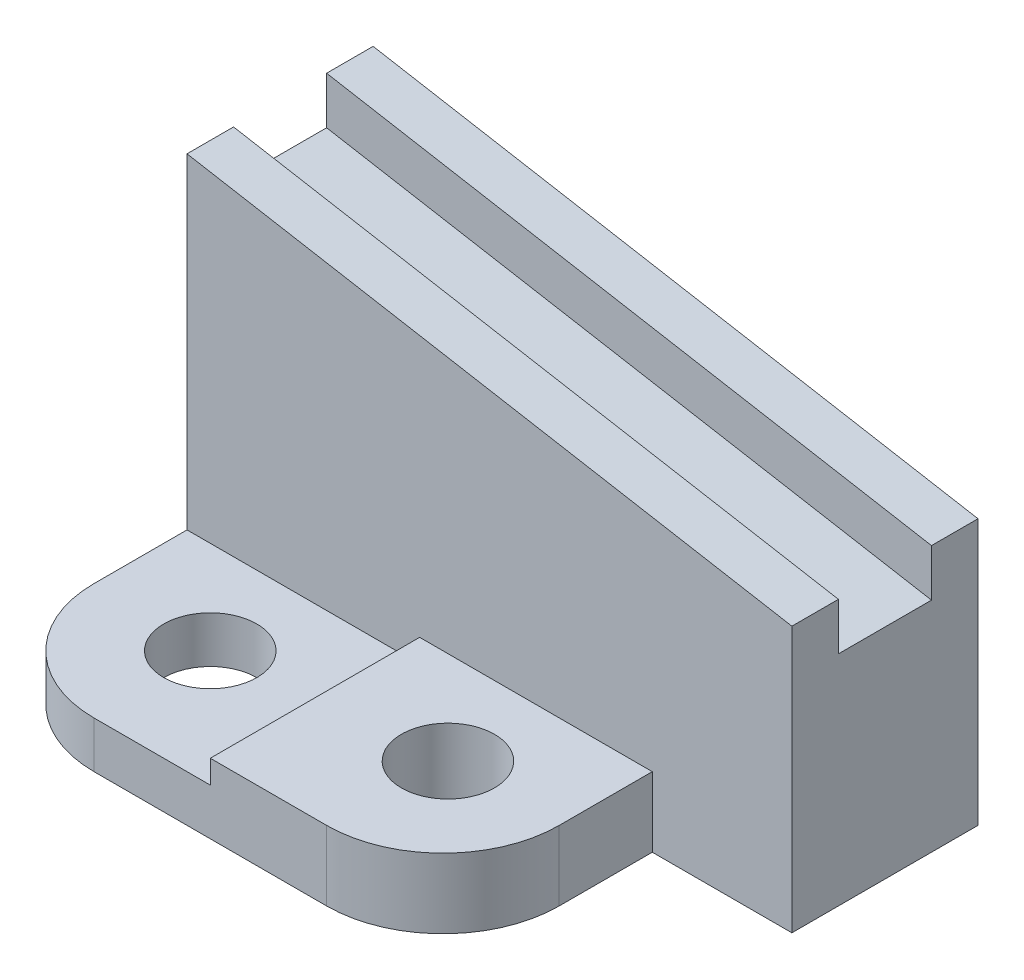
SolidWorks part; units mm, degrees
ref_plane "Plano frontal" through (0, 0, 0) normal (0, 0, 1) x (1, 0, 0)
ref_plane "Plano superior" through (0, 0, 0) normal (0, 1, 0) x (1, 0, 0)
ref_plane "Plano direito" through (0, 0, 0) normal (1, 0, 0) x (0, 0, -1)
sketch "Esboço1" plane through (0, 0, 0) normal (0, 0, 1) x (1, 0, 0)
  line L0 (-53.2953, 9.3008) -> (76.7047, 9.3008)
  line L1 (-53.2953, 9.3008) -> (-53.2953, 89.3008)
  line L2 (76.7047, 9.3008) -> (76.7047, 66.3783)
  line L3 (-53.2953, 89.3008) -> (76.7047, 66.3783)
  dimension "D1" = 100
  dimension "D2" = 80
  dimension "D3" = 130
extrude "Ressalto-extrusão1" add sketch "Esboço1" along normal blind 40
sketch "Esboço3" [suppressed] plane through (13.6643, 77.494, 0) normal (0.1736, 0.9848, 0) x (0.9848, -0.1736, 0)
  line L0 (64.0129, -40) -> (-67.9926, -40) construction
  line L1 (-71.0201, -30) -> (70.4962, -30)
  line L2 (-71.0201, -30) -> (-71.0201, -10)
  line L3 (-71.0201, -10) -> (70.4962, -10)
  line L4 (70.4962, -30) -> (70.4962, -10)
  line L5 (64.0129, 0) -> (-67.9926, 0) construction
  dimension "D1" = 10
  dimension "D2" = 10
extrude "Corte-extrusão2" [suppressed] cut sketch "Esboço3" against normal blind 10
sketch "Esboço4" plane through (13.6643, 77.494, 0) normal (0.1736, 0.9848, 0) x (0.9848, -0.1736, 0)
  line L0 (64.0129, 0) -> (-67.9926, 0) construction
  line L1 (-77.3839, -10) -> (94.2466, -10)
  line L2 (-77.3839, -10) -> (-77.3839, -30)
  line L3 (-77.3839, -30) -> (94.2466, -30)
  line L4 (94.2466, -10) -> (94.2466, -30)
  line L5 (64.0129, -40) -> (-67.9926, -40) construction
  dimension "D1" = 10
  dimension "D2" = 10
extrude "Corte-extrusão3" cut sketch "Esboço4" against normal blind 10
sketch "Esboço5" plane through (0, 0, 40) normal (0, 0, 1) x (1, 0, 0)
  line L1 (-53.2953, 9.3008) -> (46.7047, 9.3008)
  line L2 (-53.2953, 9.3008) -> (-53.2953, 24.3008)
  line L3 (-53.2953, 24.3008) -> (46.7047, 24.3008)
  line L4 (46.7047, 9.3008) -> (46.7047, 24.3008)
  dimension "D1" = 15
  dimension "D2" = 100
extrude "Ressalto-extrusão2" add sketch "Esboço5" along normal blind 45
fillet "Filete6" radius 25 1 edges at (-53.2953, 16.8008, 85) type face fillet first side face at (-53.2953, 61.52, 35.25) second side face at (-3.2953, 16.8008, 85)
fillet "Filete7" radius 25 1 edges at (46.7047, 16.8008, 85) type face fillet first side face at (9.2047, 16.8008, 85) second side face at (46.7047, 14.9258, 68.125)
sketch "Esboço7" plane through (0, 24.3008, 0) normal (0, 1, 0) x (1, 0, 0)
  line L0 (21.7047, -85) -> (-28.2953, -85) construction
  circle A0 centre (-28.2953, -60) radius 10
  circle A1 centre (22.7777, -60) radius 10
  dimension "D1" = 20
  dimension "D2" = 20
  dimension "D3" = 25
extrude "Corte-extrusão4" cut sketch "Esboço7" against normal through all
sketch "Esboço8" plane through (0, 24.3008, 0) normal (0, 1, 0) x (1, 0, 0)
  line L0 (21.7047, -85) -> (-28.2953, -85) construction
  line L1 (-53.2953, -40) -> (-3.2953, -40)
  line L2 (-53.2953, -40) -> (-53.2953, -85)
  line L3 (-53.2953, -85) -> (-3.2953, -85)
  line L4 (-3.2953, -40) -> (-3.2953, -85)
extrude "Corte-extrusão5" cut sketch "Esboço8" against normal blind 5
